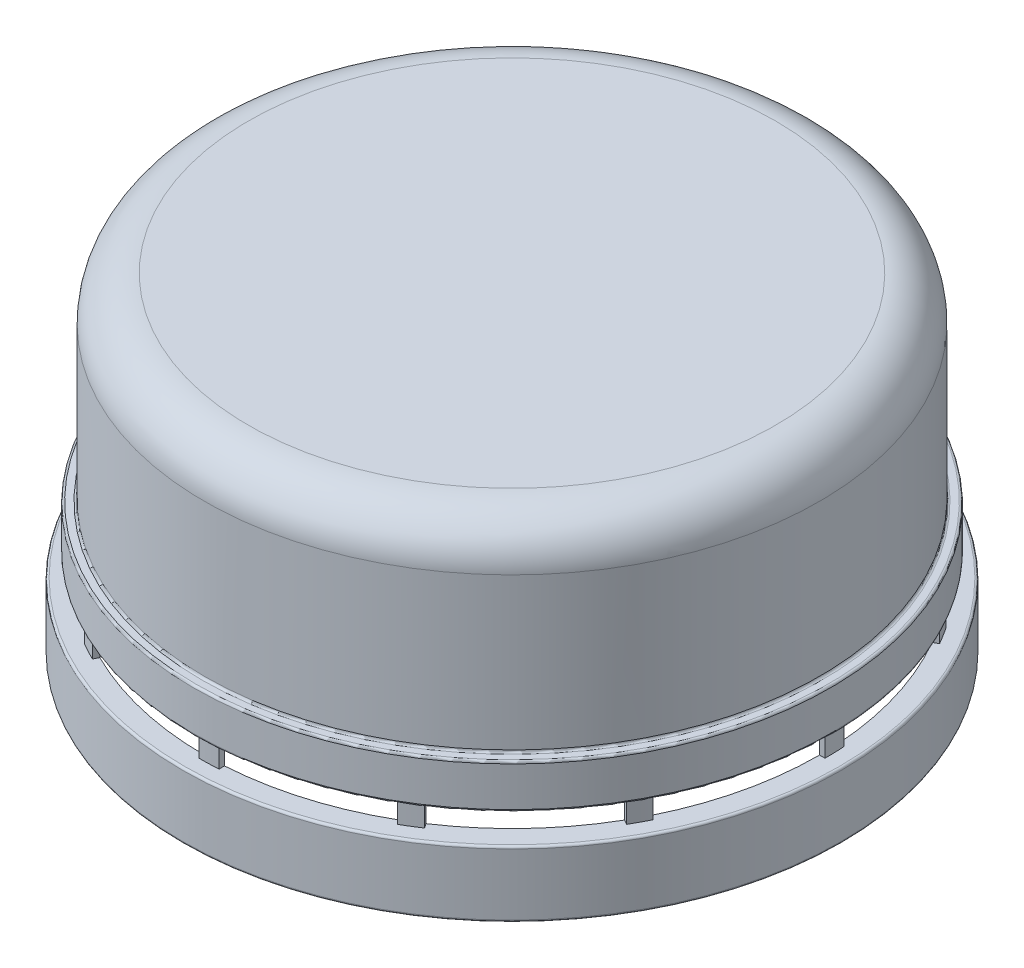
SolidWorks part; units mm, degrees
ref_plane "Front" through (0, 0, 0) normal (0, 0, 1) x (1, 0, 0)
ref_plane "Top" through (0, 0, 0) normal (0, 1, 0) x (1, 0, 0)
ref_plane "Right" through (0, 0, 0) normal (1, 0, 0) x (0, 0, -1)
sketch "Sketch1" plane through (0, 0, 0) normal (0, 0, 1) x (1, 0, 0)
  line L0 (13.25, 4) -> (13, 4.25)
  line L1 (0, 0) -> (15, 0) construction
  line L2 (0, 0) -> (0, 15) construction
  line L3 (0, 15) -> (15, 15) construction
  line L4 (15, 0) -> (15, 15) construction
  line L5 (15, 0) -> (14, 0)
  line L6 (15, 0) -> (15, 3)
  line L7 (15, 3) -> (14, 3)
  line L8 (14, 0) -> (14, 3)
  line L9 (14, 3) -> (14.25, 3)
  line L10 (14, 3) -> (14, 4)
  line L11 (14, 4) -> (14.25, 4)
  line L12 (14.25, 3) -> (14.25, 4)
  line L13 (14.5, 4) -> (13.25, 4)
  line L14 (14.5, 4) -> (14.5, 6)
  line L15 (14.5, 6) -> (13, 6)
  line L16 (13, 4.25) -> (13, 6)
  line L17 (13, 6) -> (13, 13)
  line L18 (12, 14) -> (0, 14)
  line L19 (14, 6) -> (14, 13)
  line L20 (12, 15) -> (0, 15)
  line L21 (0, 14) -> (0, 15)
  line L22 (11.5, 11.5) -> (11.75, 12.5)
  line L23 (11.25, 14) -> (11.75, 14)
  line L24 (11.25, 14) -> (11.25, 11.5)
  line L25 (11.25, 11.5) -> (11.5, 11.5)
  line L26 (11.75, 14) -> (11.75, 12.5)
  arc A0 (13, 13) -> (12, 14) centre (12, 13) ccw
  arc A1 (14, 13) -> (12, 15) centre (12, 13) ccw
  point P14 (13, 4)
  point P27 (11.75, 11.5)
  dimension "D11" = 1
  dimension "D1" = 15
  dimension "D2" = 15
  dimension "D3" = 3
  dimension "D4" = 1
  dimension "D5" = 1
  dimension "D6" = 0.25
  dimension "D7" = 2
  dimension "D8" = 0.25
  dimension "D9" = 1.5
  dimension "D10" = 1
  dimension "D14" = 0.5
  dimension "D15" = 0.25
  dimension "D16" = 2.5
  dimension "D17" = 0.25
  dimension "D18" = 1
  dimension "D13" = 1
revolve "Revolve1" add sketch "Sketch1" angle 360 about L2 region at (13.757, 5.0096, 0) region at (13.1664, 9.5, 0) region at (14.5, 1.5, 0) region at (11.4815, 12.8519, 0)
fillet "Fillet1" radius 0.1 5 edges at (0, 4, -14.5) (0, 6, -14.5) (0, 3, -15) (0, 0, -15) (0, 0, -14)
fillet "Fillet2" radius 0.1 7 edges at (0, 6, -14) (0, 4, 14) (0, 4, -13.25) (0, 4.25, -13) (0, 14, -11.25) (0, 11.5, -11.25) (0, 11.5, -11.5)
sketch "Sketch3" plane through (0, 3, 0) normal (0, 1, 0) x (1, 0, 0)
  line L0 (0, 0) -> (0, 17.5)
  line L1 (0, 0) -> (7.7811, 15.675)
  arc A0 (7.7811, 15.675) -> (0, 17.5) centre (0, 0) ccw
  dimension "D1" = 35
  dimension "D2" = 26.4
extrude "Cut-Extrude1" cut sketch "Sketch3" along normal up to surface (1 mm away) up to face at (0, 4, 13.9)
pattern_circular "CirPattern1" count 12 over 360 about axis through (0, 0, 0) along (0, -1, 0) of "Cut-Extrude1" reverse direction yes
